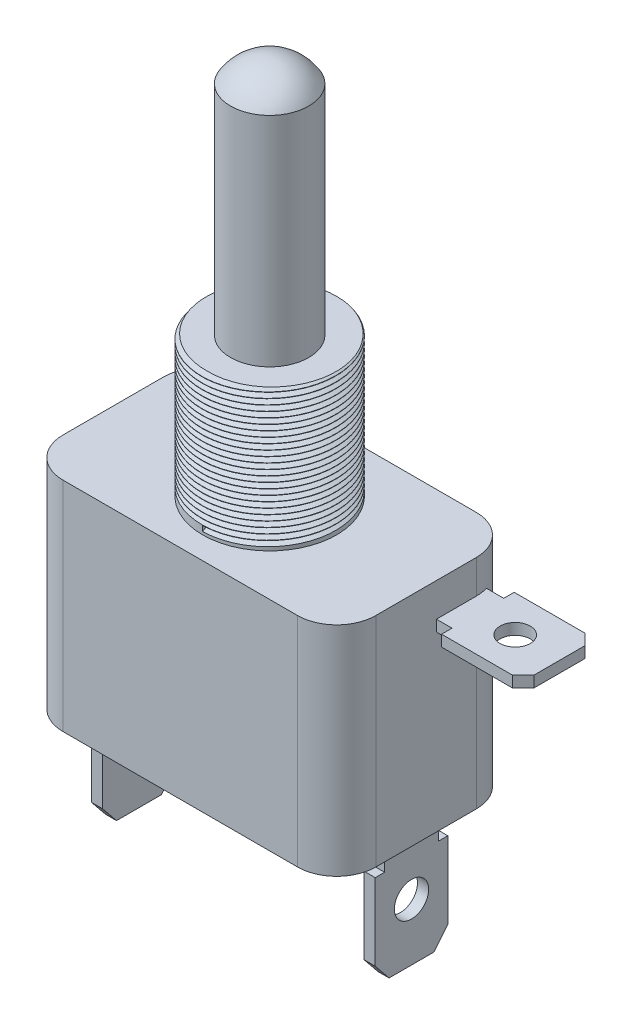
SolidWorks part; units mm, degrees
ref_plane "Front Plane" through (0, 0, 0) normal (0, 0, 1) x (1, 0, 0)
ref_plane "Top Plane" through (0, 0, 0) normal (0, 1, 0) x (1, 0, 0)
ref_plane "Right Plane" through (0, 0, 0) normal (1, 0, 0) x (0, 0, -1)
sketch "Sketch1" plane through (0, 0, 0) normal (0, 1, 0) x (1, 0, 0)
  line L1 (-14, -8) -> (14, -8)
  line L2 (-14, -8) -> (-14, 8)
  line L3 (-14, 8) -> (14, 8)
  line L4 (14, -8) -> (14, 8)
  line L5 (-14, -8) -> (14, 8) construction
  line L6 (-14, 8) -> (14, -8) construction
  point P0 (0, 0)
  dimension "D1" = 16
  dimension "D2" = 28
extrude "Boss-Extrude1" add sketch "Sketch1" along normal blind 19.5
sketch "Sketch2" plane through (0, 19.5, 0) normal (0, 1, 0) x (1, 0, 0)
  circle A0 centre (0, 0) radius 6
  dimension "D1" = 12
extrude "Boss-Extrude2" add sketch "Sketch2" along normal blind 12.5
sketch "Sketch4" plane through (0, 32, 0) normal (0, 1, 0) x (1, 0, 0)
  circle A0 centre (0, 0) radius 3.5
  dimension "D1" = 7
extrude "Boss-Extrude3" add sketch "Sketch4" along normal blind 19.5
dome "Dome1" faces to dome 1 distance 2 reverse direction no elliptical dome no face at (0, 51.5, 3.5) parameters "D1"=2
sketch "Sketch5" plane through (0, 32, 0) normal (0, 1, 0) x (1, 0, 0)
  circle A0 centre (0, 0) radius 6 construction
  circle A1 centre (0, 0) radius 6
curve "Helix/Spiral1" pitch 0.5 height 12 radius 6 centre (0, 32, 0) axis (0, -1, 0) start towards (0, 0, 1)
sketch "Sketch6" plane through (0, 0, 0) normal (1, 0, 0) x (0, 0, -1)
  line L1 (-5.5938, 32) -> (-6.2031, 32.3518)
  line L2 (-6.2031, 32.3518) -> (-6.2031, 31.6482)
  line L3 (-6.2031, 31.6482) -> (-5.5938, 32)
  circle A0 centre (-6, 32) radius 0.2031 construction
sweep "Cut-Sweep1" cut profiles "Sketch6" path "Helix/Spiral1" align with end faces yes
sketch "Sketch7" plane through (0, 0, 0) normal (0, -1, 0) x (1, 0, 0)
  line L0 (-14, -8) -> (-14, 8) construction
  line L1 (11.7, 3.25) -> (12.7, 3.25)
  line L2 (11.7, 3.25) -> (11.7, -3.25)
  line L3 (11.7, -3.25) -> (12.7, -3.25)
  line L4 (12.7, 3.25) -> (12.7, -3.25)
  line L5 (11.7, 3.25) -> (12.7, -3.25) construction
  line L6 (11.7, -3.25) -> (12.7, 3.25) construction
  line L7 (-12.7, 3.25) -> (-11.7, 3.25)
  line L8 (-12.7, 3.25) -> (-12.7, -3.25)
  line L9 (-12.7, -3.25) -> (-11.7, -3.25)
  line L10 (-11.7, 3.25) -> (-11.7, -3.25)
  line L11 (-12.7, 3.25) -> (-11.7, -3.25) construction
  line L12 (-12.7, -3.25) -> (-11.7, 3.25) construction
  line L13 (14, 8) -> (14, -8) construction
  point P0 (12.2, 0)
  point P5 (-12.2, 0)
  point P10 (0, 0)
  point P11 (0, 0)
  dimension "D1" = 6.5
  dimension "D2" = 1
  dimension "D3" = 1.3
  dimension "D4" = 1.3
extrude "Boss-Extrude4" add sketch "Sketch7" along normal blind 10.5
sketch "Sketch8" plane through (12.7, 0, 0) normal (1, 0, 0) x (0, 0, -1)
  line L0 (-3.25, -8.9627) -> (-2.0079, -10.5)
  line L1 (-3.25, -10.5) -> (-3.25, 0) construction
  line L2 (3.25, -10.5) -> (-3.25, -10.5) construction
  line L3 (-2.0079, -10.5) -> (-3.25, -10.5)
  line L4 (-3.25, -10.5) -> (-3.25, -8.9627)
  line L5 (2.0079, -10.5) -> (3.25, -8.9627)
  line L6 (3.25, -10.5) -> (3.25, 0) construction
  line L7 (3.25, -8.9627) -> (3.25, -10.5)
  line L8 (3.25, -10.5) -> (2.0079, -10.5)
  line L10 (3.25, 0) -> (2.4119, 0)
  line L11 (3.25, 0) -> (3.25, -2.0983)
  line L12 (3.25, -2.0983) -> (2.4119, -2.0983)
  line L13 (2.4119, 0) -> (2.4119, -2.0983)
  line L14 (-3.25, 0) -> (-2.4119, 0)
  line L15 (-3.25, 0) -> (-3.25, -2.0983)
  line L16 (-3.25, -2.0983) -> (-2.4119, -2.0983)
  line L17 (-2.4119, 0) -> (-2.4119, -2.0983)
  circle A0 centre (0, -5.3972) radius 1.5342
  point P26 (0, 0)
extrude "Cut-Extrude1" cut sketch "Sketch8" against normal through all
sketch "Sketch9" plane through (14, 0, 0) normal (1, 0, 0) x (0, 0, -1)
  line L0 (8, 19.5) -> (8, 0) construction
  line L1 (6.5, 16.5) -> (0, 16.5)
  line L2 (6.5, 16.5) -> (6.5, 15.5)
  line L3 (6.5, 15.5) -> (0, 15.5)
  line L4 (0, 16.5) -> (0, 15.5)
  line L5 (-8, 19.5) -> (8, 19.5) construction
  dimension "D1" = 1
  dimension "D2" = 6.5
  dimension "D3" = 1.5
  dimension "D4" = 3
extrude "Boss-Extrude5" add sketch "Sketch9" along normal blind 8.7
sketch "Sketch10" plane through (0, 16.5, 0) normal (0, 1, 0) x (1, 0, 0)
  line L0 (14, 6.5) -> (14, 0) construction
  line L1 (14, 5.5654) -> (15.3945, 5.5654)
  line L2 (14, 5.5654) -> (14, 6.5)
  line L3 (14, 6.5) -> (15.3945, 6.5)
  line L4 (15.3945, 5.5654) -> (15.3945, 6.5)
  line L5 (22.7, 6.5) -> (14, 6.5) construction
  line L6 (22.7, 0) -> (14, 0) construction
  line L7 (14, 0.9346) -> (15.3945, 0.9346)
  line L8 (14, 0.9346) -> (14, 0)
  line L9 (14, 0) -> (15.3945, 0)
  line L10 (15.3945, 0.9346) -> (15.3945, 0)
  line L11 (22.7, 6.5) -> (22.7, 0) construction
  line L12 (21.7401, 6.5) -> (22.7, 5.5401)
  line L13 (22.7, 5.5401) -> (22.7, 6.5)
  line L14 (22.7, 6.5) -> (21.7401, 6.5)
  line L15 (22.7, 0) -> (22.7, 0.9599)
  line L16 (22.7, 0.9599) -> (21.7401, 0)
  line L17 (21.7401, 0) -> (22.7, 0)
  circle A0 centre (18.7346, 3.25) radius 1.3519
  point P18 (22.7, 3.25)
extrude "Cut-Extrude2" cut sketch "Sketch10" against normal up to next
fillet "Fillet1" radius 3.5 4 edges at (-14, 9.75, 8) (-14, 9.75, -8) (14, 9.75, -8) (14, 9.75, 8)
